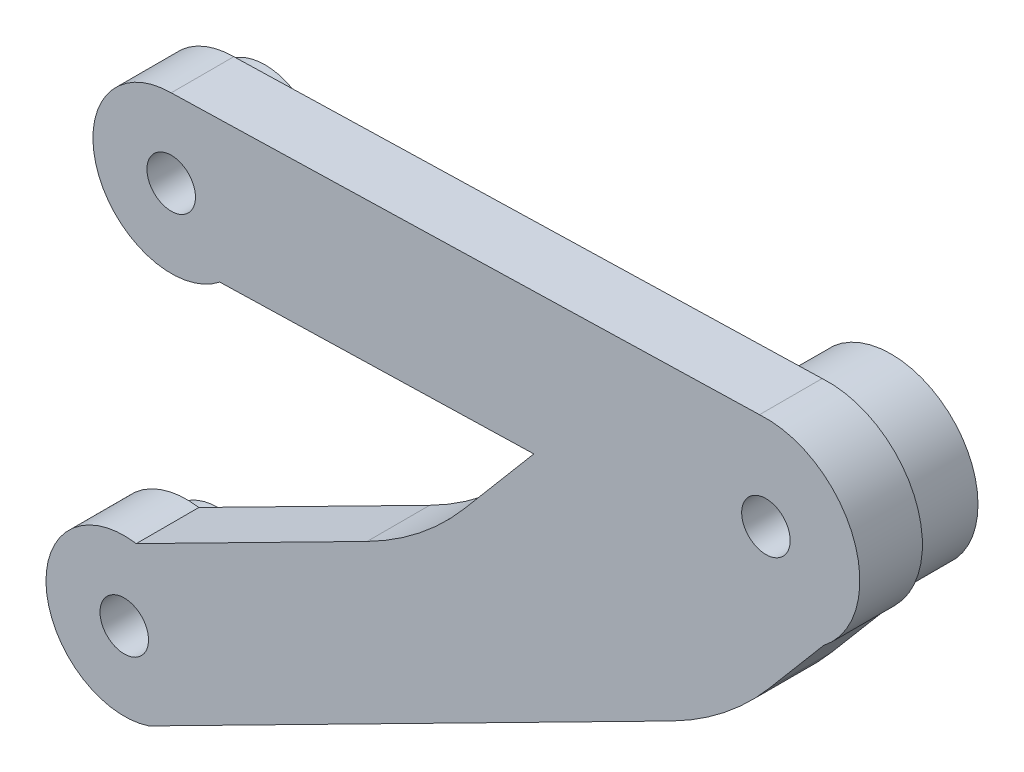
SolidWorks part; units mm, degrees
ref_plane "Front Plane" through (0, 0, 0) normal (0, 0, 1) x (1, 0, 0)
ref_plane "Top Plane" through (0, 0, 0) normal (0, 1, 0) x (1, 0, 0)
ref_plane "Right Plane" through (0, 0, 0) normal (1, 0, 0) x (0, 0, -1)
sketch "Sketch2" plane through (0, 0, 0) normal (0, 0, 1) x (1, 0, 0)
  line L0 (0, 0) -> (0, 26) construction
  line L1 (41, 26) -> (0, 26) construction
  line L2 (0, 0) -> (0, 26) construction
  line L3 (0, 26) -> (3, 26) construction
  line L4 (1.5758, -4.7452) -> (38.5983, 14.0699)
  line L5 (38.5983, 14.0699) -> (44.6837, 21.264)
  line L6 (3, 31) -> (40.5909, 31.986)
  line L10 (26.171, 22.6047) -> (19.1158, 14.2643)
  line L11 (19.1158, 14.2643) -> (0.7692, 4.9405)
  line L12 (6.1016, 22.0783) -> (26.171, 22.6047)
  circle A0 centre (0, 0) radius 1.55
  circle A1 centre (41, 26) radius 1.55
  circle A2 centre (3, 26) radius 1.55
  arc A3 (0.7692, 4.9405) -> (1.5758, -4.7452) centre (0, 0) ccw
  arc A4 (44.6837, 21.264) -> (40.5909, 31.986) centre (41, 26) ccw
  arc A5 (3, 31) -> (6.1016, 22.0783) centre (3, 26) ccw
  dimension "D1" = 3.1
  dimension "D2" = 3.1
  dimension "D3" = 3.1
  dimension "D8" = 10
  dimension "D9" = 12
  dimension "D10" = 10
  dimension "D5" = 41
  dimension "D6" = 26
  dimension "D7" = 3
  dimension "D11" = 9
  dimension "D12" = 9
  dimension "D13" = 15
extrude "Boss-Extrude1" add sketch "Sketch2" along normal blind 2 and the other way blind 2 contours L6 A5 A3 L4 L5 A4 A0 A1 A2 region at (-4.3468, -0.3619, 0)
fillet "Fillet1" radius 20 2 edges at (38.5983, 14.0699, 0) (19.1158, 14.2643, 0)
sketch "Sketch3" plane through (0, 0, 2) normal (0, 0, 1) x (1, 0, 0)
  line L0 (44.6837, 21.264) -> (26.4129, -0.3351)
  line L1 (41.2064, 17.1532) -> (44.6837, 21.264) construction
  line L2 (26.4129, -0.3351) -> (34.7488, -7.3866)
  line L3 (34.7488, -7.3866) -> (43.0769, 2.4586)
  line L4 (44.6837, 21.264) -> (53.0197, 14.2125)
  line L5 (53.0197, 14.2125) -> (44.6915, 4.3673)
  line L6 (43.0769, 2.4586) -> (30.2338, -2.2575)
  line L7 (30.2338, -2.2575) -> (47.213, 17.8147)
  line L8 (47.213, 17.8147) -> (44.6915, 4.3673)
  line L9 (30.2338, -2.2575) -> (29.588, -3.021) construction
  line L10 (47.213, 17.8147) -> (47.8588, 18.5781) construction
  dimension "D1" = 1
  dimension "D2" = 2.5
extrude "Boss-Extrude2" [suppressed] add sketch "Sketch3" against normal up to surface (10 mm away) up to face at (1.55, 0, -2)
fillet "Fillet2" [suppressed] radius 1
sketch "Sketch4" plane through (0, 0, 2) normal (0, 0, 1) x (1, 0, 0)
  line L7 (41.2064, 17.1532) -> (44.6837, 21.264) construction
  line L8 (0, 0) -> (50000, 0) construction
  line L17 (44.6837, 21.264) -> (47.1283, 17.3372)
  line L18 (41.0014, 32) -> (48.527, 32)
  line L19 (48.527, 32) -> (54.0756, 21.2914)
  line L20 (52.0144, 16.8475) -> (52.5897, 16.0258)
  line L21 (52.461, 17.1603) -> (53.0363, 16.3386)
  line L22 (50.5241, 19.4512) -> (-28628.2978, 40977.0534) construction
  arc A0 (41.0014, 32) -> (44.6837, 21.264) centre (41, 26) cw
  arc A1 (44.6837, 21.264) -> (40.5909, 31.986) centre (41, 26) ccw construction
  arc A3 (52.461, 17.1603) -> (52.0144, 16.8475) centre (50.5241, 19.4512) ccw
  arc A4 (47.1283, 17.3372) -> (52.5897, 16.0258) centre (50.5241, 19.4512) ccw
  arc A5 (53.0363, 16.3386) -> (54.0756, 21.2914) centre (50.5241, 19.4512) ccw
  dimension "D1" = 6
  dimension "D2" = 8
  dimension "D3" = 55
extrude "Boss-Extrude3" [suppressed] add sketch "Sketch4" against normal up to surface (4 mm away) up to face at (1.55, 0, -2)
fillet "Fillet3" [suppressed] radius 6
sketch "Sketch7" plane through (0, 0, -2) normal (0, 0, -1) x (-1, 0, 0)
  circle A0 centre (-41, 26) radius 1.55
  circle A1 centre (-41, 26) radius 5.55
  dimension "D1" = 4
extrude "Boss-Extrude4" add sketch "Sketch7" along normal blind 4
sketch "Sketch8" plane through (0, 0, -2) normal (0, 0, -1) x (-1, 0, 0)
  circle A0 centre (-3, 26) radius 1.55
  circle A1 centre (-3, 26) radius 3.55
  circle A2 centre (0, 0) radius 1.55
  circle A3 centre (0, 0) radius 3.55
  dimension "D1" = 2
  dimension "D2" = 2
extrude "Boss-Extrude5" add sketch "Sketch8" along normal blind 2
